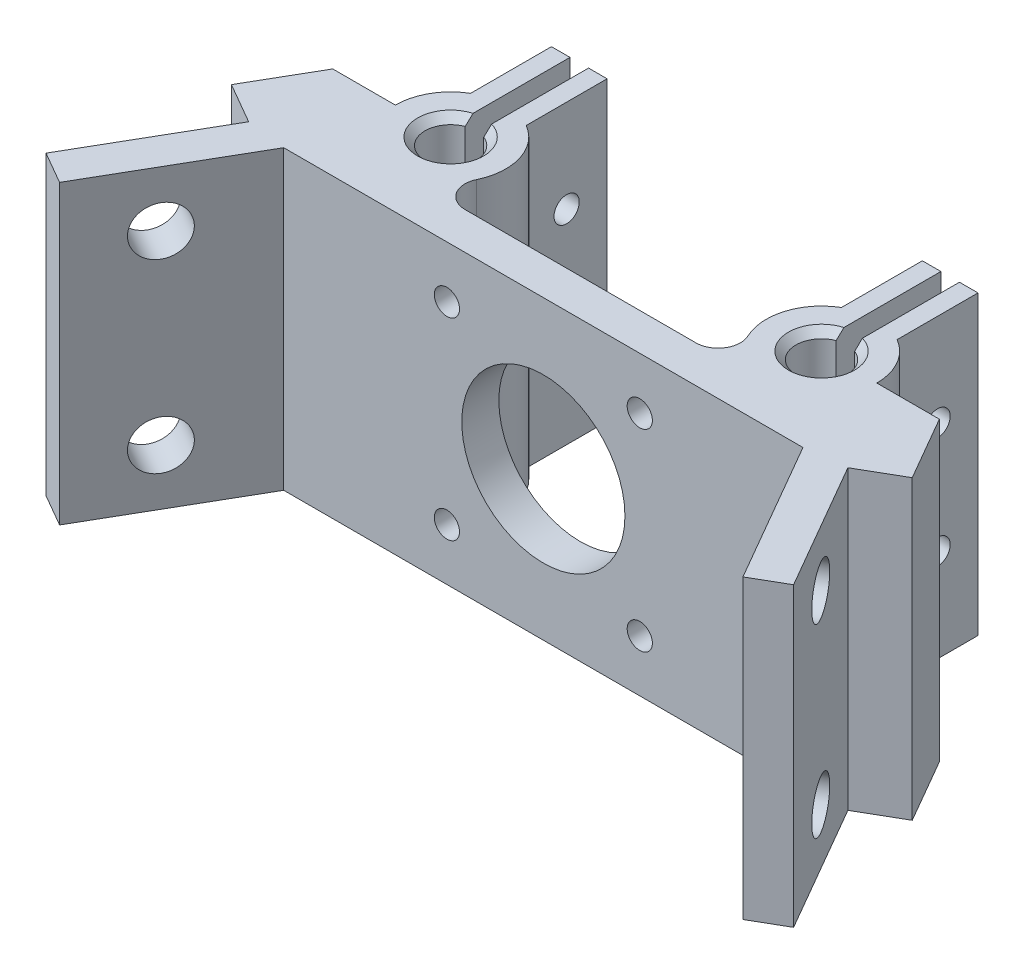
SolidWorks part; units mm, degrees
ref_plane "Front Plane" through (0, 0, 0) normal (0, 0, 1) x (1, 0, 0)
ref_plane "Top Plane" through (0, 0, 0) normal (0, 1, 0) x (1, 0, 0)
ref_plane "Right Plane" through (0, 0, 0) normal (1, 0, 0) x (0, 0, -1)
sketch "Sketch1" plane through (0, 0, 0) normal (0, 1, 0) x (1, 0, 0)
  line L0 (0, 116.7614) -> (0, -100.8523) construction
  line L1 (23.75, 120.7156) -> (23.75, 134.8444)
  line L2 (28.75, 134.8444) -> (28.75, 123.9374)
  line L3 (25, -2.1466) -> (25, 14.9187) construction
  line L4 (23.75, 134.8444) -> (21.25, 134.8444)
  line L5 (21.25, 134.8444) -> (21.25, 123.9374)
  line L6 (26.25, 134.8444) -> (28.75, 134.8444)
  line L7 (26.25, 120.7156) -> (26.25, 134.8444)
  line L8 (-25, -0.2491) -> (-25, 16.8161) construction
  line L9 (-26.25, 120.7156) -> (-26.25, 134.8444)
  line L10 (-26.25, 134.8444) -> (-28.75, 134.8444)
  line L11 (-21.25, 134.8444) -> (-21.25, 123.9374)
  line L12 (-23.75, 134.8444) -> (-21.25, 134.8444)
  line L13 (-28.75, 134.8444) -> (-28.75, 123.9374)
  line L14 (-23.75, 120.7156) -> (-23.75, 134.8444)
  line L15 (-15.5685, 110) -> (15.5685, 110)
  line L16 (-35, 105) -> (35, 105)
  line L17 (-32.45, 117.5) -> (-40.889, 117.5)
  line L18 (0, 110) -> (-95.2628, -55) construction
  line L19 (-95.2628, -55) -> (95.2628, -55) construction
  line L20 (95.2628, -55) -> (0, 110) construction
  line L21 (-40.889, 117.5) -> (-45.889, 108.8397)
  line L22 (-50.3897, 88.3442) -> (-46.0596, 85.8442)
  line L23 (-46.0596, 85.8442) -> (-35, 105)
  line L24 (46.0596, 85.8442) -> (35, 105)
  line L25 (50.3897, 88.3442) -> (46.0596, 85.8442)
  line L26 (50.3897, 88.3442) -> (40.3897, 105.6647)
  line L27 (32.45, 117.5) -> (40.889, 117.5)
  line L28 (-50.3897, 88.3442) -> (-40.3897, 105.6647)
  line L29 (-40.3897, 105.6647) -> (-45.889, 108.8397)
  line L30 (40.3897, 105.6647) -> (45.889, 108.8397)
  line L31 (40.889, 117.5) -> (45.889, 108.8397)
  arc A0 (21.25, 123.9374) -> (18.2761, 114.2919) centre (25, 117.5) ccw
  arc A1 (23.75, 120.7156) -> (26.25, 120.7156) centre (25, 117.5) ccw
  arc A2 (-23.75, 120.7156) -> (-26.25, 120.7156) centre (-25, 117.5) cw
  arc A3 (-21.25, 123.9374) -> (-18.2761, 114.2919) centre (-25, 117.5) cw
  circle A4 centre (0, 0) radius 110 construction
  circle A5 centre (0, 0) radius 55 construction
  arc A6 (15.5685, 110) -> (18.2761, 114.2919) centre (15.5685, 113) ccw
  arc A7 (-18.2761, 114.2919) -> (-15.5685, 110) centre (-15.5685, 113) ccw
  arc A8 (-28.75, 123.9374) -> (-32.45, 117.5) centre (-25, 117.5) ccw
  arc A9 (28.75, 123.9374) -> (32.45, 117.5) centre (25, 117.5) cw
  point P12 (23.75, 124.8444)
  point P13 (26.25, 124.8444)
  point P27 (-26.25, 124.8444)
  point P28 (-23.75, 124.8444)
  point P67 (0, 0)
  dimension "D2" = 6.9
  dimension "D3" = 4
  dimension "D5" = 2.5
  dimension "D10" = 120
  dimension "D11" = 10
  dimension "D7" = 220
  dimension "D13" = 3
  dimension "D14" = 7.5
  dimension "D1" = 50
  dimension "D4" = 10
  dimension "D6" = 2.5
  dimension "D8" = 5
  dimension "D9" = 70
  dimension "D12" = 5
  dimension "D15" = 20
  dimension "D16" = 6.35
extrude "Boss-Extrude1" add sketch "Sketch1" along normal blind 40 contours A3 L11 L12 L14 A2 L9 L10 L13 | A1 L1 L4 L5 A0 L2 L6 L7 | L15 A3 L16 A0 region at (25, 0, -112.9294)
sketch "Sketch2" plane through (0, 0, 0) normal (1, 0, 0) x (0, 0, -1)
  line L0 (129.3909, 40) -> (129.3909, 0) construction
  line L3 (134.8444, 20) -> (113.9952, 20) construction
  line L4 (134.8444, 40) -> (134.8444, 0) construction
  line L6 (134.8444, 40) -> (123.9374, 40) construction
  line L7 (134.8444, 0) -> (123.9374, 0) construction
  circle A0 centre (129.3909, 27.5) radius 1.7
  circle A1 centre (129.3909, 12.5) radius 1.7
  dimension "D1" = 3.4
  dimension "D2" = 15
extrude "Cut-Extrude1" cut sketch "Sketch2" against normal mid plane 57.5
sketch "Sketch4" plane through (0, 0, -105) normal (0, 0, 1) x (1, 0, 0)
  line L1 (-13, 7) -> (13, 7) construction
  line L2 (-13, 7) -> (-13, 33) construction
  line L3 (-13, 33) -> (13, 33) construction
  line L4 (13, 7) -> (13, 33) construction
  line L5 (-13, 7) -> (13, 33) construction
  line L6 (-13, 33) -> (13, 7) construction
  line L7 (17.75, 2.25) -> (-17.75, 2.25)
  line L8 (17.75, 2.25) -> (17.75, 37.75)
  line L9 (17.75, 37.75) -> (-17.75, 37.75)
  line L10 (-17.75, 2.25) -> (-17.75, 37.75)
  line L11 (17.75, 2.25) -> (-17.75, 37.75) construction
  line L12 (17.75, 37.75) -> (-17.75, 2.25) construction
  circle A0 centre (-13, 33) radius 1.7
  circle A1 centre (13, 33) radius 1.7
  circle A2 centre (13, 7) radius 1.7
  circle A3 centre (-13, 7) radius 1.7
  circle A4 centre (0, 20) radius 11
  circle A5 centre (-13, 33) radius 2.9337 construction
  point P0 (0, 20)
  point P16 (0, 20)
  dimension "D2" = 3.4
  dimension "D5" = 22
  dimension "D7" = 5.8674
  dimension "D1" = 26
  dimension "D4" = 20
  dimension "D6" = 35.5
  dimension "D3" = 4
extrude "Cut-Extrude2" cut sketch "Sketch4" against normal blind 20 contours A0 | A4 | A1 | A2 | A3 region at (-13, 33, -105) region at (13, 33, -105) region at (13, 7, -105) region at (-13, 7, -105) region at (0, 20, -105)
chamfer "Chamfer1" distance 1 angle 45 2 edges at (25, 40, -114.05) (-25, 40, -114.05)
sketch "Sketch5" plane through (-76.0465, 0, -43.9054) normal (-0.866, 0, -0.5) x (-0.5, 0, 0.866)
  line L0 (-51.3135, 20) -> (-71.3135, 20) construction
  line L1 (-51.3135, 40) -> (-51.3135, 0) construction
  line L2 (-71.3135, 40) -> (-71.3135, 0) construction
  line L3 (-61.3135, 20) -> (-61.3135, 32.5) construction
  line L4 (-61.3135, 20) -> (-61.3135, 7.5) construction
  circle A0 centre (-61.3135, 32.5) radius 3.3
  circle A1 centre (-61.3135, 7.5) radius 3.3
  dimension "D1" = 10
  dimension "D2" = 6.6
  dimension "D3" = 25
extrude "Cut-Extrude3" cut sketch "Sketch5" against normal up to next
mirror "Mirror1" about plane through (0, 0, 0) normal (1, 0, 0) of "Cut-Extrude3"
equation "\"RodSpacing\"= 50"
equation "\"D1@Sketch1\"=\"RodSpacing\""
equation "\"Clamp_Gap\"=2.5"
equation "\"D5@Sketch1\"= \"Clamp_Gap\""
equation "\"D6@Sketch1\"=\"Clamp_Gap\""
equation "\"D1@Cut-Extrude1\"=\"RodSpacing\"+(3*\"Clamp_Gap\")"
equation "\"Smooth_Rod_Hole\"=6.9"
equation "\"D2@Sketch1\"=\"Smooth_Rod_Hole\""
equation "\"Inside_Spacing\"=70"
equation "\"D9@Sketch1\"=\"Inside_Spacing\""
